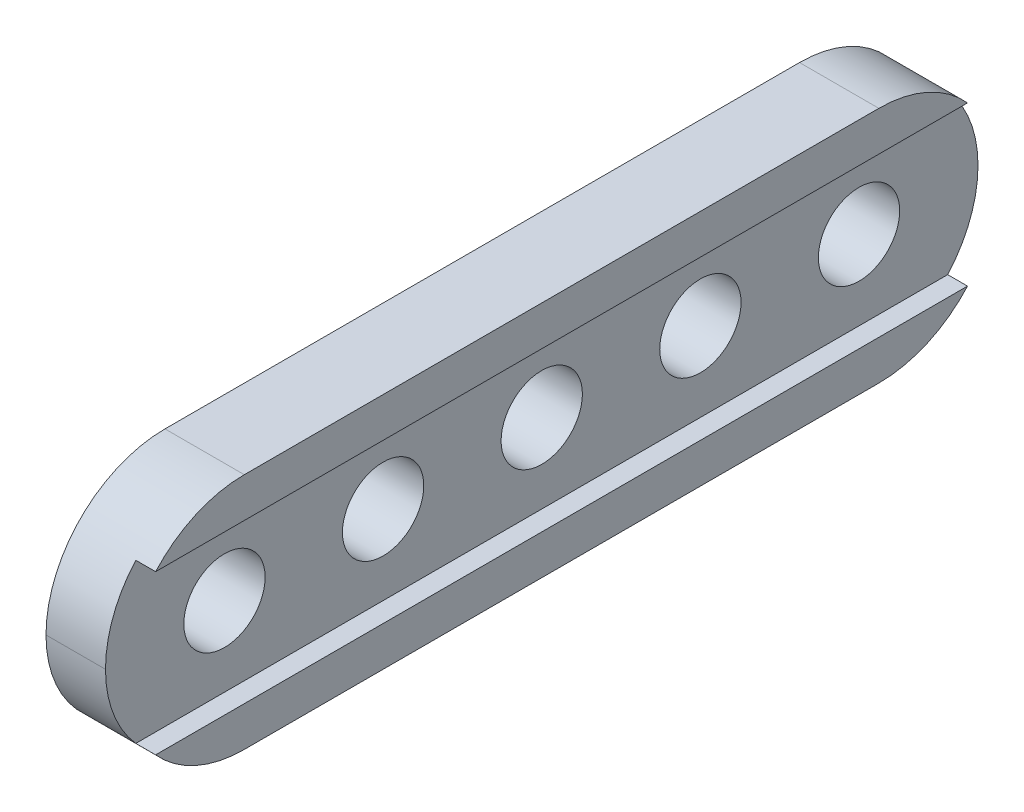
SolidWorks part; units mm, degrees
ref_plane "Front Plane" through (0, 0, 0) normal (0, 0, 1) x (1, 0, 0)
ref_plane "Top Plane" through (0, 0, 0) normal (0, 1, 0) x (1, 0, 0)
ref_plane "Right Plane" through (0, 0, 0) normal (1, 0, 0) x (0, 0, -1)
sketch "Sketch1" plane through (0, 0, 0) normal (0, 0, 1) x (1, 0, 0)
  line L0 (3, 6) -> (0, 6) construction
  line L1 (0, 0) -> (4, 0)
  line L2 (0, 0) -> (0, 12)
  line L3 (0, 12) -> (4, 12)
  line L4 (4, 0) -> (4, 2)
  line L5 (4, 10) -> (3, 10)
  line L7 (4, 2) -> (3, 2)
  line L8 (3, 10) -> (3, 2)
  line L9 (4, 10) -> (4, 12)
  dimension "D1" = 4
  dimension "D2" = 12
  dimension "D3" = 8
  dimension "D4" = 1
extrude "Boss-Extrude1" add sketch "Sketch1" against normal blind 44
ref_plane "Plane1" through (0, 0, -22) normal (0, 0, 1) x (1, 0, 0)
fillet "Fillet1" radius 6 4 edges at (2, 12, 0) (2, 0, 0) (2, 0, -44) (2, 12, -44)
sketch "Sketch2" plane through (0, 0, 0) normal (-1, 0, 0) x (0, 0, 1)
  circle A0 centre (-38, 6) radius 2.05
  dimension "D1" = 4.1
extrude "Cut-Extrude1" cut sketch "Sketch2" against normal through all
pattern_linear "LPattern1" count 3 spacing 8 along (0, 0, 1) of "Cut-Extrude1"
mirror "Mirror1" about plane through (0, 0, -22) normal (0, 0, 1) of "LPattern1", "Cut-Extrude1"
